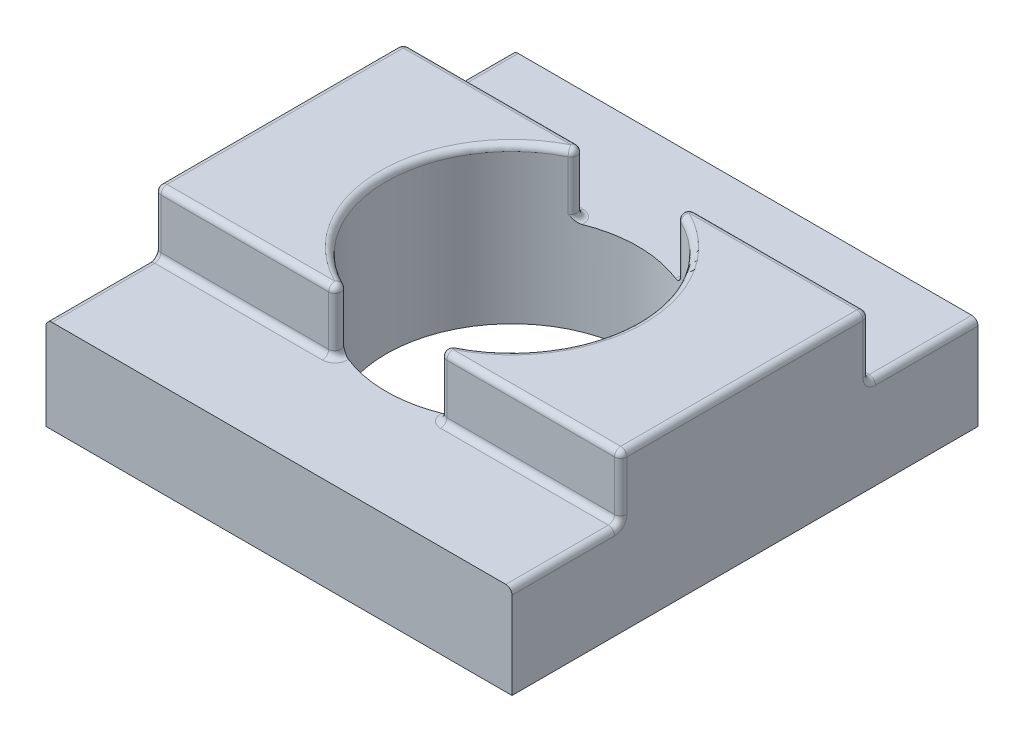
SolidWorks part; units mm, degrees
ref_plane "Front Plane" through (0, 0, 0) normal (0, 0, 1) x (1, 0, 0)
ref_plane "Top Plane" through (0, 0, 0) normal (0, 1, 0) x (1, 0, 0)
ref_plane "Right Plane" through (0, 0, 0) normal (1, 0, 0) x (0, 0, -1)
sketch "Sketch1" plane through (0, 0, 0) normal (0, 1, 0) x (1, 0, 0)
  line L1 (-7.5, 7.5) -> (7.5, 7.5)
  line L2 (-7.5, 7.5) -> (-7.5, -7.5)
  line L3 (-7.5, -7.5) -> (7.5, -7.5)
  line L4 (7.5, 7.5) -> (7.5, -7.5)
  line L5 (-7.5, 7.5) -> (7.5, -7.5) construction
  line L6 (-7.5, -7.5) -> (7.5, 7.5) construction
  point P0 (0, 0)
  dimension "D1" = 15
  dimension "D2" = 15
extrude "Boss-Extrude1" add sketch "Sketch1" along normal blind 5
sketch "Sketch2" plane through (-7.5, 0, 0) normal (-1, 0, 0) x (0, 0, 1)
  line L0 (-7.5, 5) -> (7.5, 5) construction
  line L1 (7.5, 5) -> (4, 5)
  line L2 (7.5, 5) -> (7.5, 3)
  line L3 (7.5, 3) -> (4, 3)
  line L4 (4, 5) -> (4, 3)
  line L5 (-7.5, 5) -> (-4, 5)
  line L6 (-7.5, 5) -> (-7.5, 3)
  line L7 (-7.5, 3) -> (-4, 3)
  line L8 (-4, 5) -> (-4, 3)
  dimension "D1" = 8
  dimension "D3" = 2
extrude "Cut-Extrude1" cut sketch "Sketch2" against normal through all both and the other way through all
sketch "Sketch3" plane through (0, 0, 0) normal (0, -1, 0) x (1, 0, 0)
  circle A0 centre (0, 0) radius 4.05
  dimension "D1" = 8.1
extrude "Cut-Extrude2" cut sketch "Sketch3" against normal through all both and the other way through all
fillet "Fillet1" radius 0.2 4 edges at (-0.6344, 4, -4) (0.6344, 4, -4) (0.6344, 4, 4) (-0.6344, 4, 4)
fillet "Fillet2" radius 0.2 28 edges at (7.5, 3, 5.75) (-7.5, 3, 5.75) (-7.5, 3, -5.75) (7.5, 3, -5.75) (-1.7087, 3, -3.846) (1.7087, 3, -3.846) (-1.7087, 3, 3.846) (4.7016, 3, 4) (7.5, 5, 0) (4.7016, 5, 4) (1.7087, 5, 3.846) (4.05, 5, 0) (1.7087, 5, -3.846) (4.7016, 5, -4) (-1.7087, 5, 3.846) (-4.7016, 5, 4) (-7.5, 5, 0) (-4.7016, 5, -4) (-1.7087, 5, -3.846) (-4.05, 5, 0) (-7.5, 4, 4) (-7.5, 4, -4) (7.5, 4, 4) (7.5, 4, -4) (-4.7016, 3, -4) (4.7016, 3, -4) (-4.7016, 3, 4) (1.7087, 3, 3.846)
